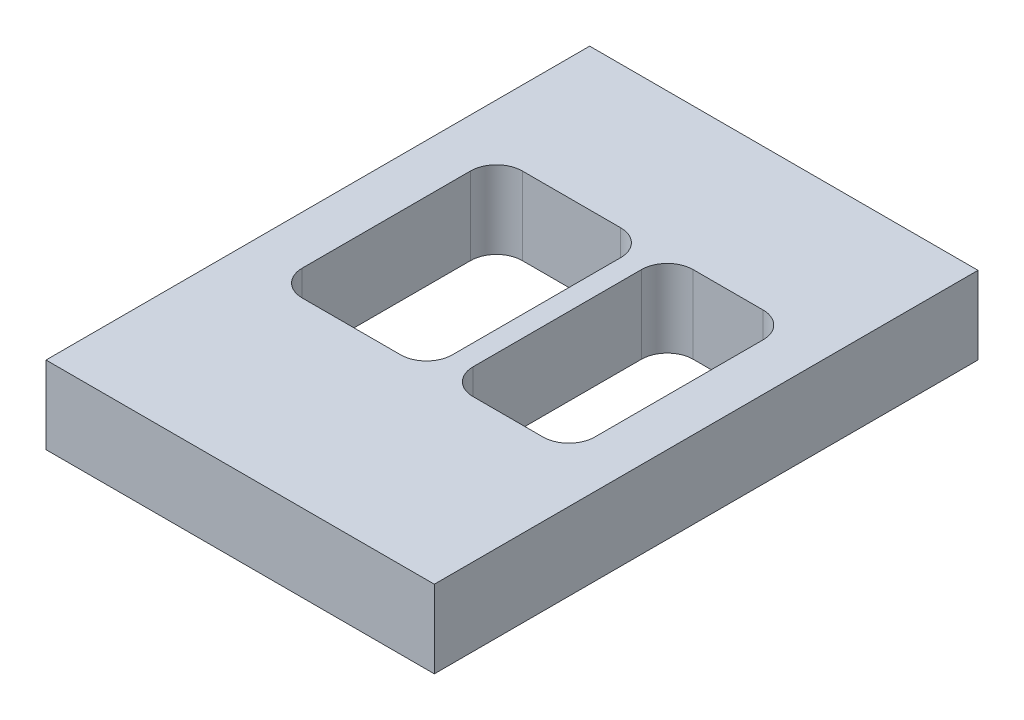
SolidWorks part; units mm, degrees
material "K110"
ref_plane "Front Plane" through (0, 0, 0) normal (0, 0, 1) x (1, 0, 0)
ref_plane "Top Plane" through (0, 0, 0) normal (0, 1, 0) x (1, 0, 0)
ref_plane "Right Plane" through (0, 0, 0) normal (1, 0, 0) x (0, 0, -1)
sketch "Sketch1" plane through (0, 0, 0) normal (0, 1, 0) x (1, 0, 0)
  line L1 (-75, 105) -> (75, 105)
  line L2 (-75, 105) -> (-75, -105)
  line L3 (-75, -105) -> (75, -105)
  line L4 (75, 105) -> (75, -105)
  line L5 (-75, 105) -> (75, -105) construction
  line L6 (-75, -105) -> (75, 105) construction
  point P0 (0, 0)
  dimension "D1" = 210
  dimension "D2" = 150
extrude "Boss-Extrude1" add sketch "Sketch1" against normal blind 30
sketch "Sketch2" plane through (0, 0, 0) normal (0, 1, 0) x (1, 0, 0)
  line L3 (24.75, -27.27) -> (24.75, -11.27) construction
  line L4 (27.75, -8.27) -> (33.88, -8.27) construction
  line L5 (35.88, -6.27) -> (35.88, 11.73) construction
  line L6 (33.88, 13.73) -> (27.75, 13.73) construction
  line L7 (24.75, 42.73) -> (24.75, 16.73) construction
  line L8 (-37.37, 42.73) -> (-13.25, 42.73) construction
  line L9 (-13.25, 42.73) -> (-13.25, 34.23) construction
  line L10 (-14.75, 32.73) -> (-29.37, 32.73) construction
  line L11 (-35.37, 26.73) -> (-35.37, -6.27) construction
  line L12 (-29.37, -12.27) -> (-14.75, -12.27) construction
  line L13 (-13.25, -27.27) -> (-13.25, -13.77) construction
  line L14 (-37.37, -27.27) -> (-13.25, -27.27) construction
  line L15 (-40.37, 39.73) -> (-40.37, -24.27) construction
  line L19 (24.75, -27.27) -> (24.75, -11.27)
  line L20 (27.75, -8.27) -> (33.88, -8.27)
  line L21 (35.88, -6.27) -> (35.88, 11.73)
  line L22 (33.88, 13.73) -> (27.75, 13.73)
  line L23 (24.75, 42.73) -> (24.75, 16.73)
  line L24 (-37.37, 42.73) -> (-13.25, 42.73)
  line L25 (-13.25, 42.73) -> (-13.25, 34.23)
  line L26 (-14.75, 32.73) -> (-29.37, 32.73)
  line L27 (-35.37, 26.73) -> (-35.37, -6.27)
  line L28 (-29.37, -12.27) -> (-14.75, -12.27)
  line L29 (-13.25, -27.27) -> (-13.25, -13.77)
  line L30 (-37.37, -27.27) -> (-13.25, -27.27)
  line L31 (-40.37, 39.73) -> (-40.37, -24.27)
  line L32 (40.88, 42.73) -> (40.88, 39.73) construction
  line L33 (37.88, 42.73) -> (40.88, 42.73) construction
  line L34 (40.88, -27.27) -> (37.88, -27.27) construction
  line L35 (40.88, -24.27) -> (40.88, -27.27) construction
  line L36 (24.75, 42.73) -> (37.88, 42.73) construction
  line L37 (40.88, 39.73) -> (40.88, -24.27) construction
  line L38 (37.88, -27.27) -> (24.75, -27.27) construction
  line L39 (24.75, 42.73) -> (37.88, 42.73)
  line L40 (40.88, 39.73) -> (40.88, -24.27)
  line L41 (37.88, -27.27) -> (24.75, -27.27)
  arc A0 (27.75, -8.27) -> (24.75, -11.27) centre (27.75, -11.27) ccw construction
  arc A1 (33.88, -8.27) -> (35.88, -6.27) centre (33.88, -6.27) ccw construction
  arc A2 (35.88, 11.73) -> (33.88, 13.73) centre (33.88, 11.73) ccw construction
  arc A3 (24.75, 16.73) -> (27.75, 13.73) centre (27.75, 16.73) ccw construction
  arc A4 (-37.37, 42.73) -> (-40.37, 39.73) centre (-37.37, 39.73) ccw construction
  arc A5 (-14.75, 32.73) -> (-13.25, 34.23) centre (-14.75, 34.23) ccw construction
  arc A6 (-29.37, 32.73) -> (-35.37, 26.73) centre (-29.37, 26.73) ccw construction
  arc A7 (-35.37, -6.27) -> (-29.37, -12.27) centre (-29.37, -6.27) ccw construction
  arc A8 (-13.25, -13.77) -> (-14.75, -12.27) centre (-14.75, -13.77) ccw construction
  arc A9 (-40.37, -24.27) -> (-37.37, -27.27) centre (-37.37, -24.27) ccw construction
  arc A10 (27.75, -8.27) -> (24.75, -11.27) centre (27.75, -11.27) ccw
  arc A11 (33.88, -8.27) -> (35.88, -6.27) centre (33.88, -6.27) ccw
  arc A12 (35.88, 11.73) -> (33.88, 13.73) centre (33.88, 11.73) ccw
  arc A13 (24.75, 16.73) -> (27.75, 13.73) centre (27.75, 16.73) ccw
  arc A14 (-37.37, 42.73) -> (-40.37, 39.73) centre (-37.37, 39.73) ccw
  arc A15 (-14.75, 32.73) -> (-13.25, 34.23) centre (-14.75, 34.23) ccw
  arc A16 (-29.37, 32.73) -> (-35.37, 26.73) centre (-29.37, 26.73) ccw
  arc A17 (-35.37, -6.27) -> (-29.37, -12.27) centre (-29.37, -6.27) ccw
  arc A18 (-13.25, -13.77) -> (-14.75, -12.27) centre (-14.75, -13.77) ccw
  arc A19 (-40.37, -24.27) -> (-37.37, -27.27) centre (-37.37, -24.27) ccw
  arc A20 (40.88, 39.73) -> (37.88, 42.73) centre (37.88, 39.73) ccw construction
  arc A21 (37.88, -27.27) -> (40.88, -24.27) centre (37.88, -24.27) ccw construction
  arc A22 (40.88, 39.73) -> (37.88, 42.73) centre (37.88, 39.73) ccw
  arc A23 (37.88, -27.27) -> (40.88, -24.27) centre (37.88, -24.27) ccw
sketch "Sketch3" plane through (0, 0, 0) normal (0, 1, 0) x (1, 0, 0)
  line L1 (-56.25, 50.23) -> (1.75, 50.23)
  line L2 (-56.25, 50.23) -> (-56.25, -34.77)
  line L3 (-56.25, -34.77) -> (1.75, -34.77)
  line L4 (1.75, 50.23) -> (1.75, -34.77)
  line L5 (9.75, 50.23) -> (56.75, 50.23)
  line L6 (9.75, 50.23) -> (9.75, -34.77)
  line L7 (9.75, -34.77) -> (56.75, -34.77)
  line L8 (56.75, 50.23) -> (56.75, -34.77)
  line L15 (24.75, 42.73) -> (24.75, 16.73) construction
  line L16 (-13.25, 42.73) -> (-13.25, 34.23) construction
  point P8 (-128.166, 22.3916)
  dimension "D1" = 85
  dimension "D4" = 15
  dimension "D5" = 15
  dimension "D6" = 47
  dimension "D7" = 58
extrude "Cut-Extrude1" cut sketch "Sketch3" against normal up to next
fillet "Fillet1" radius 10 8 edges at (9.75, -15, -50.23) (56.75, -15, 34.77) (56.75, -15, -50.23) (9.75, -15, 34.77) (-56.25, -15, 34.77) (1.75, -15, 34.77) (1.75, -15, -50.23) (-56.25, -15, -50.23)
